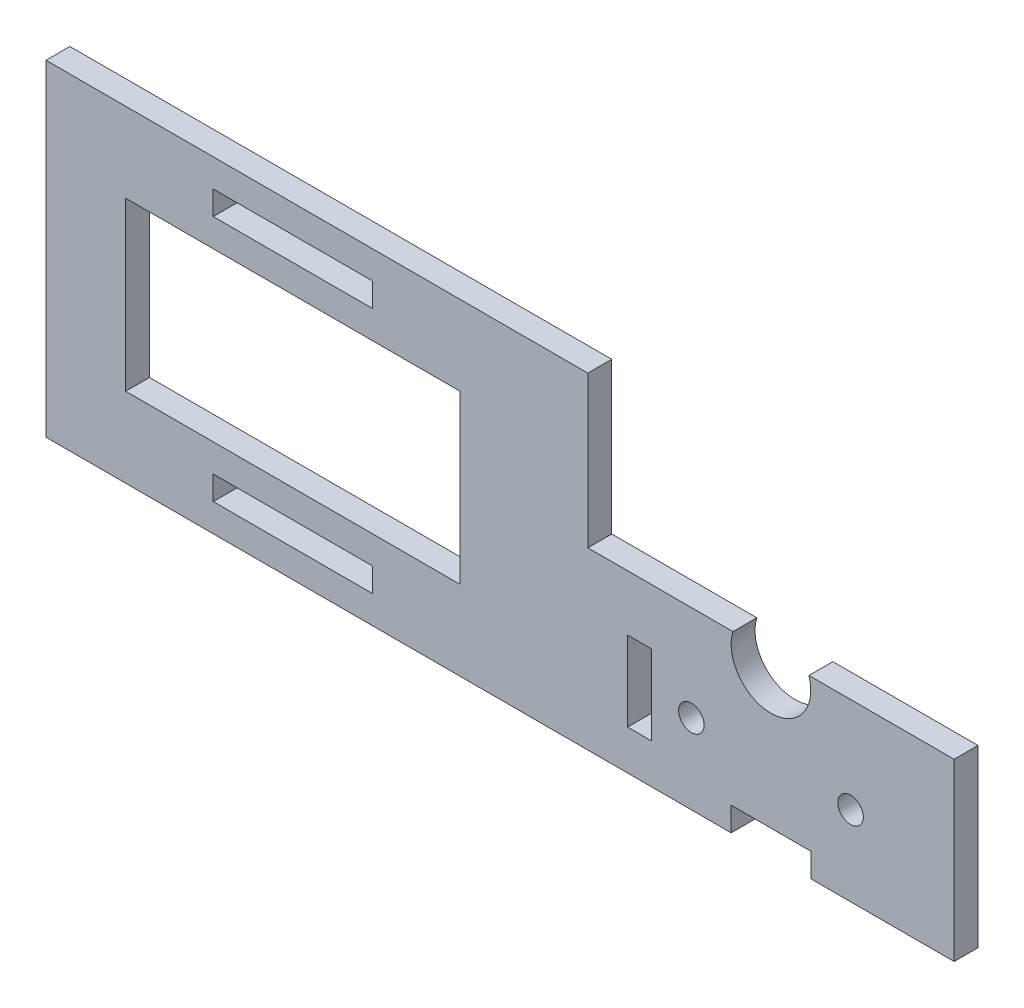
SolidWorks part; units mm, degrees
ref_plane "Plano frontal" through (0, 0, 0) normal (0, 0, 1) x (1, 0, 0)
ref_plane "Plano superior" through (0, 0, 0) normal (0, 1, 0) x (1, 0, 0)
ref_plane "Plano direito" through (0, 0, 0) normal (1, 0, 0) x (0, 0, -1)
sketch "Esboço1" plane through (0, 0, 0) normal (0, 0, 1) x (1, 0, 0)
  line L0 (0, 20.5) -> (0, 0) construction
  line L5 (15, 15) -> (18, 15) construction
  line L6 (18, 5) -> (18, 15) construction
  line L15 (10, 10) -> (-10, 10) construction
  line L16 (15, 5) -> (18, 5) construction
  line L21 (-15, 5) -> (-18, 5)
  line L22 (-15, 5) -> (-15, 15)
  line L27 (-15, 15) -> (-18, 15)
  line L28 (-18, 5) -> (-18, 15)
  line L29 (-15, 5) -> (-18, 15) construction
  line L30 (-15, 15) -> (-18, 5) construction
  line L35 (15, 5) -> (15, 15) construction
  line L36 (23, 0) -> (23, 22)
  line L37 (23, 22) -> (-23, 22)
  line L43 (-23, 0) -> (23, 0)
  line L49 (-23, 0) -> (-91.05, 0)
  line L50 (-91.05, 0) -> (-91.05, 41)
  line L55 (-91.05, 41) -> (-23, 41)
  line L56 (-23, 41) -> (-23, 22)
  line L61 (-60.05, 20.5) -> (-60.05, 0) construction
  line L62 (-81.05, 10) -> (-39.05, 10)
  line L63 (-81.05, 10) -> (-81.05, 31)
  line L64 (-81.05, 31) -> (-39.05, 31)
  line L65 (-39.05, 10) -> (-39.05, 31)
  line L66 (-81.05, 10) -> (-39.05, 31) construction
  line L67 (-81.05, 31) -> (-39.05, 10) construction
  line L68 (-60.05, 20.5) -> (-91.05, 20.5) construction
  line L69 (-60.05, 31) -> (-60.05, 41) construction
  line L70 (-50.05, 37.5) -> (-70.05, 37.5)
  line L71 (-50.05, 37.5) -> (-50.05, 34.5)
  line L72 (-50.05, 34.5) -> (-70.05, 34.5)
  line L73 (-70.05, 37.5) -> (-70.05, 34.5)
  line L74 (-50.05, 37.5) -> (-70.05, 34.5) construction
  line L75 (-50.05, 34.5) -> (-70.05, 37.5) construction
  line L76 (-50.05, 6.5) -> (-70.05, 6.5)
  line L77 (-70.05, 3.5) -> (-70.05, 6.5)
  line L78 (-50.05, 3.5) -> (-70.05, 3.5)
  line L79 (-50.05, 3.5) -> (-50.05, 6.5)
  line L81 (-5, 0) -> (5, 0)
  line L82 (-5, 0) -> (-5, 3)
  line L83 (-5, 3) -> (5, 3)
  line L84 (5, 0) -> (5, 3)
  line L85 (-5, 0) -> (5, 3) construction
  line L86 (-5, 3) -> (5, 0) construction
  circle A0 centre (0, 20.5) radius 5
  circle A1 centre (10, 10) radius 1.6
  circle A2 centre (-10, 10) radius 1.6
  circle A3 centre (-84.8, 15.5) radius 1.6 construction
  circle A5 centre (-84.8, 25.5) radius 1.6 construction
  circle A6 centre (-35.3, 25.5) radius 1.6 construction
  circle A7 centre (-35.3, 15.5) radius 1.6 construction
  point P0 (0, 20.5)
  point P12 (0, 0)
  point P13 (-16.5, 10)
  point P24 (-60.05, 20.5)
  point P26 (0, 0)
  point P43 (-50, 20.5)
  point P44 (-60.05, 36)
  point P49 (0, 1.5)
  point P61 (0, 10)
  dimension "D1" = 10
  dimension "D3" = 3.2
  dimension "D11" = 10
  dimension "D12" = 49.5
  dimension "D2" = 20
  dimension "D4" = 5
  dimension "D5" = 10
  dimension "D6" = 10
  dimension "D7" = 3
  dimension "D8" = 42
  dimension "D9" = 21
  dimension "D10" = 10
  dimension "D13" = 14.7
  dimension "D14" = 50
  dimension "D15" = 3
  dimension "D16" = 20
  dimension "D17" = 5
  dimension "D18" = 5
  dimension "D19" = 7
  dimension "D20" = 3
  dimension "D21" = 10
extrude "Ressalto-extrusão1" add sketch "Esboço1" along normal blind 3 contours L6 A0 region at (-36.869, 17.321, 0)
